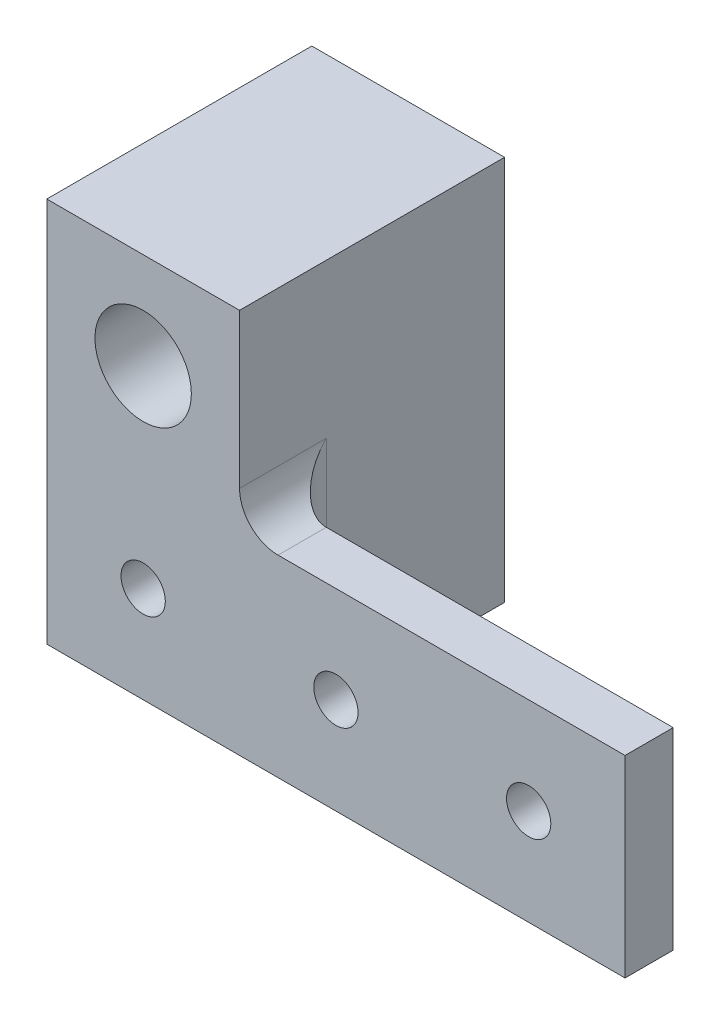
SolidWorks part; units mm, degrees
ref_plane "Front Plane" through (0, 0, 0) normal (0, 0, 1) x (1, 0, 0)
ref_plane "Top Plane" through (0, 0, 0) normal (0, 1, 0) x (1, 0, 0)
ref_plane "Right Plane" through (0, 0, 0) normal (1, 0, 0) x (0, 0, -1)
sketch "Sketch1" plane through (0, 0, 0) normal (0, 0, 1) x (1, 0, 0)
  line L0 (0, 0) -> (0, 50.8)
  line L1 (0, 50.8) -> (25.4, 50.8)
  line L2 (25.4, 50.8) -> (25.4, 25.4)
  line L3 (25.4, 25.4) -> (76.2, 25.4)
  line L4 (76.2, 25.4) -> (76.2, 0)
  line L5 (76.2, 0) -> (0, 0)
  dimension "D1" = 50.8
  dimension "D2" = 25.4
  dimension "3" = 76.2
extrude "Boss-Extrude1" add sketch "Sketch1" along normal blind 34.925
sketch "Sketch2" plane through (0, 0, 34.925) normal (0, 0, 1) x (1, 0, 0)
  line L0 (25.4, 50.8) -> (0, 50.8) construction
  line L1 (25.4, 25.4) -> (25.4, 50.8) construction
  line L2 (0, 0) -> (76.2, 0) construction
  circle A0 centre (12.7, 38.1) radius 2.921
  circle A1 centre (12.7, 12.7) radius 2.921
  circle A2 centre (38.1, 12.7) radius 2.921
  circle A3 centre (63.5, 12.7) radius 2.921
  dimension ".23" = 5.842
  dimension "D2" = 12.7
  dimension "D3" = 12.7
  dimension "D4" = 12.7
  dimension "D5" = 3
extrude "Cut-Extrude1" cut sketch "Sketch2" against normal through all
sketch "Sketch3" plane through (0, 0, 34.925) normal (0, 0, 1) x (1, 0, 0)
  line L0 (25.4, 50.8) -> (0, 50.8) construction
  line L1 (0, 0) -> (4.7625, 0)
  line L2 (0, 0) -> (0, 50.8)
  line L3 (0, 50.8) -> (4.7625, 50.8)
  line L4 (4.7625, 0) -> (4.7625, 50.8)
  dimension "D1" = 4.7625
sketch "Sketch4" plane through (0, 0, 0) normal (0, -1, 0) x (1, 0, 0)
  line L1 (76.2, 0) -> (25.4, 0)
  line L2 (76.2, 0) -> (76.2, 28.575)
  line L3 (76.2, 28.575) -> (25.4, 28.575)
  line L4 (25.4, 0) -> (25.4, 28.575)
  dimension "D1" = 28.575
  dimension "D2" = 50.8
extrude "Cut-Extrude3" cut sketch "Sketch4" against normal through all
fillet "Fillet1" radius 5.08 2 edges at (25.4, 12.7, 28.575) (25.4, 25.4, 31.75)
sketch "Sketch5" plane through (0, 0, 34.925) normal (0, 0, 1) x (1, 0, 0)
  circle A0 centre (12.7, 38.1) radius 6.35
  dimension "0." = 12.7
extrude "Cut-Extrude4" cut sketch "Sketch5" against normal blind 22.225
